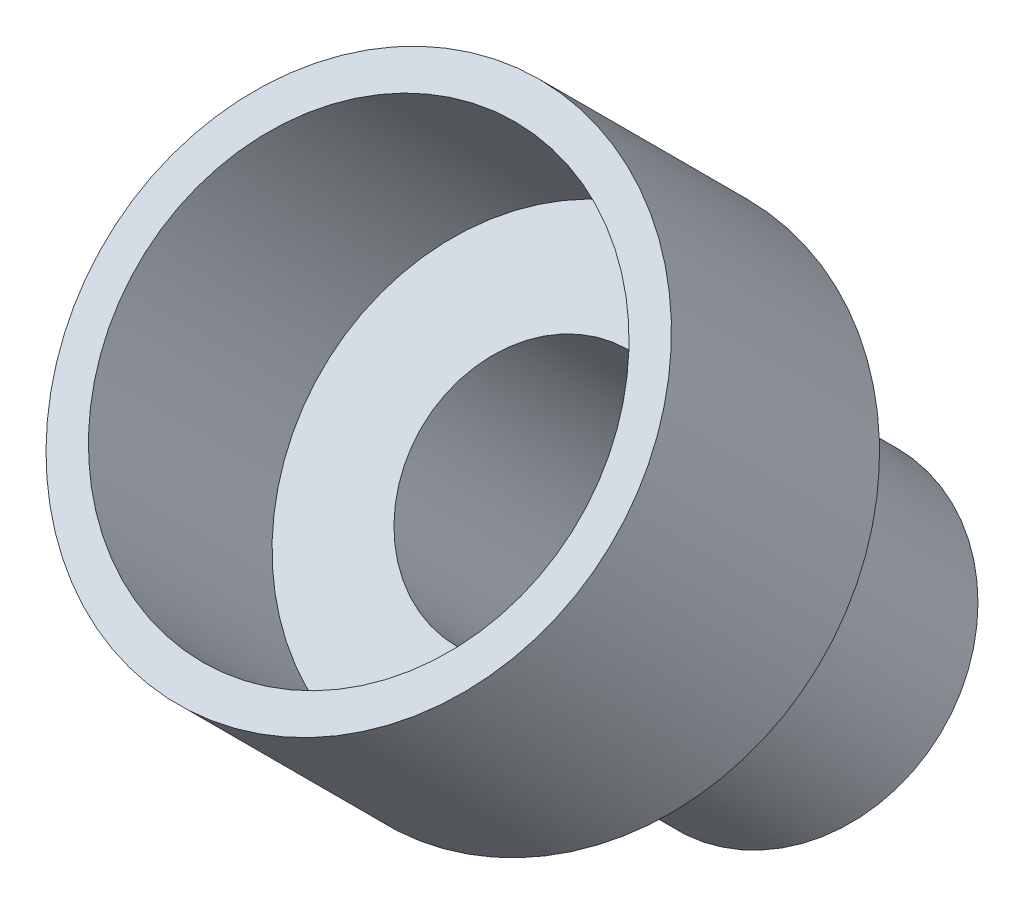
SolidWorks part; units mm, degrees
ref_plane "Front Plane" through (0, 0, 0) normal (0, 0, 1) x (1, 0, 0)
ref_plane "Top Plane" through (0, 0, 0) normal (0, 1, 0) x (1, 0, 0)
ref_plane "Right Plane" through (0, 0, 0) normal (1, 0, 0) x (0, 0, -1)
sketch "Sketch1" plane through (0, 0, 0) normal (1, 0, 0) x (0, 0, -1)
  line L0 (0, 0) -> (0, 92.1557) construction
  line L1 (0, 92.1557) -> (-111.3251, 203.4808) construction
  line L2 (0, 92.1557) -> (100.574, 192.7296) construction
  line L3 (-51.442, 125.5665) -> (-40.8354, 114.9599)
  line L4 (-40.8354, 114.9599) -> (-36.7696, 119.0257)
  line L5 (-36.7696, 119.0257) -> (-22.6274, 104.8836)
  line L6 (-22.6274, 104.8836) -> (-24.0416, 103.4694)
  line L7 (-51.442, 125.5665) -> (-52.8562, 124.1522)
  line L8 (-52.8562, 124.1522) -> (-40.8354, 112.1314)
  line L9 (-40.8354, 112.1314) -> (-36.7696, 116.1973)
  line L10 (-36.7696, 116.1973) -> (-24.0416, 103.4694)
  dimension "D1" = 90
  dimension "D2" = 135
  dimension "D3" = 25.5
  dimension "D4" = 15
  dimension "D5" = 14
  dimension "D6" = 20
  dimension "D7" = 25
  dimension "D8" = 2
  dimension "D9" = 2
  dimension "D10" = 2
revolve "Revolve1" add sketch "Sketch1" angle 360 about L1
sketch "Sketch2" plane through (0, 0, 0) normal (1, 0, 0) x (0, 0, -1)
  line L7 (-42.4264, 134.5821) -> (0, 92.1557) construction
  line L8 (0, 92.1557) -> (42.4264, 134.5821) construction
  line L9 (0, 92.1557) -> (0, 0) construction
  line L10 (-30, 104.5821) -> (-12.4264, 122.1557)
  line L11 (12.4264, 122.1557) -> (30.9634, 103.6187)
  line L12 (-30, 79.7293) -> (-12.4264, 62.1557)
  line L13 (12.4264, 62.1557) -> (30.9634, 80.6926)
  line L14 (-12.4264, 122.1557) -> (12.4264, 122.1557)
  line L16 (-30, 104.5821) -> (-30, 79.7293)
  line L17 (-12.4264, 62.1557) -> (12.4264, 62.1557)
  line L19 (-33.4108, 143.5977) -> (-51.442, 125.5665) construction
  line L21 (-11.3137, 116.1973) -> (-24.0416, 128.9252) construction
  line L22 (30.9634, 103.6187) -> (30.9634, 80.6926)
  circle A0 centre (0, 92.1557) radius 28.1134
  dimension "D1" = 30
  dimension "D2" = 30
  dimension "D3" = 30
  dimension "D5" = 30
extrude "Boss-Extrude1" [suppressed] add sketch "Sketch2" along normal blind 15 and the other way blind 15
pattern_circular "CirPattern1" count 2 every 90 of "Revolve1" reverse direction yes
sketch "Sketch4" [suppressed] plane through (0, 0, 0) normal (1, 0, 0) x (0, 0, -1)
  line L0 (0, 62.1557) -> (0, 3.1356) construction
  line L1 (-12.4264, 62.1557) -> (12.4264, 62.1557) construction
  line L2 (-14.5, 68.6222) -> (-14.5, 52.1557)
  line L3 (-14.5, 52.1557) -> (-24.5, 52.1557)
  line L4 (-24.5, 52.1557) -> (-24.5, 47.1557)
  line L6 (-16.5, 47.1557) -> (-16.5, 32.1557)
  line L7 (-16.5, 32.1557) -> (-20.5, 32.1557)
  line L8 (-20.5, 32.1557) -> (-20.5, 47.1557)
  line L10 (-12.5, 47.1557) -> (-12.5, 66.6222)
  line L11 (-14.5, 68.6222) -> (-12.5, 66.6222)
  line L12 (-24.5, 47.1557) -> (-20.5, 47.1557)
  line L13 (-16.5, 47.1557) -> (-12.5, 47.1557)
  dimension "D1" = 25
  dimension "D2" = 2
  dimension "D3" = 15
  dimension "D5" = 10
  dimension "D6" = 10
  dimension "D7" = 8
  dimension "D8" = 4
revolve "Revolve2" [suppressed] add sketch "Sketch4" angle 360 about L0
sketch "Sketch5" [suppressed] plane through (15, 0, 0) normal (1, 0, 0) x (0, 0, -1)
  circle A0 centre (0, 92.1557) radius 28.1134
extrude "Cut-Extrude1" [suppressed] cut sketch "Sketch5" against normal blind 41
sketch "Sketch6" [suppressed] plane through (0, 67.291, 67.291) normal (0, 0.7071, 0.7071) x (1, 0, 0)
  circle A0 centre (0, 65.1639) radius 7
extrude "Cut-Extrude2" [suppressed] cut sketch "Sketch6" against normal blind 41
sketch "Sketch7" [suppressed] plane through (0, 67.291, -67.291) normal (0, 0.7071, -0.7071) x (1, 0, 0)
  circle A0 centre (0, -65.1639) radius 7
extrude "Cut-Extrude3" [suppressed] cut sketch "Sketch7" against normal blind 41
sketch "Sketch8" [suppressed] plane through (0, 62.1557, 0) normal (0, -1, 0) x (1, 0, 0)
  circle A0 centre (0, 0) radius 12.5
extrude "Cut-Extrude4" [suppressed] cut sketch "Sketch8" against normal blind 41
fillet "Fillet1" [suppressed] radius 3
sketch "Sketch9" [suppressed] plane through (15, 0, 0) normal (1, 0, 0) x (0, 0, -1)
  line L2 (-30, 104.5821) -> (-12.4264, 122.1557)
  line L3 (12.4264, 122.1557) -> (30.9634, 103.6187)
  line L4 (-30, 79.7293) -> (-12.4264, 62.1557)
  line L5 (12.4264, 62.1557) -> (30.9634, 80.6926)
  line L6 (-12.4264, 122.1557) -> (12.4264, 122.1557)
  line L7 (-30, 104.5821) -> (-30, 79.7293)
  line L8 (-12.4264, 62.1557) -> (12.4264, 62.1557)
  line L9 (30.9634, 103.6187) -> (30.9634, 80.6926)
extrude "Boss-Extrude2" [suppressed] add sketch "Sketch9" against normal blind 2
sketch "Sketch10" [suppressed] plane through (-15, 0, 0) normal (-1, 0, 0) x (0, 0, 1)
  line L2 (-30, 104.5821) -> (-12.4264, 122.1557)
  line L3 (12.4264, 122.1557) -> (30.9634, 103.6187)
  line L4 (-30, 79.7293) -> (-12.4264, 62.1557)
  line L5 (12.4264, 62.1557) -> (30.9634, 80.6926)
  line L6 (-12.4264, 122.1557) -> (12.4264, 122.1557)
  line L7 (-30, 104.5821) -> (-30, 79.7293)
  line L8 (-12.4264, 62.1557) -> (12.4264, 62.1557)
  line L9 (30.9634, 103.6187) -> (30.9634, 80.6926)
extrude "Boss-Extrude3" [suppressed] add sketch "Sketch10" against normal blind 2
fillet "Fillet2" [suppressed] radius 3
ref_plane "Plane1" [suppressed] through (0, 2.1557, 0) normal (0, -1, 0) x (-1, 0, 0)
sketch "Sketch11" [suppressed] plane through (0, 2.1557, 0) normal (0, -1, 0) x (-1, 0, 0)
  line L1 (0, 29.7335) -> (-25.75, 14.8668)
  line L2 (-25.75, 14.8668) -> (-25.75, -14.8668)
  line L3 (-25.75, -14.8668) -> (0, -29.7335)
  line L4 (0, -29.7335) -> (25.75, -14.8668)
  line L5 (25.75, -14.8668) -> (25.75, 14.8668)
  line L6 (25.75, 14.8668) -> (0, 29.7335)
  circle A0 centre (0, 0) radius 19.75
  circle A1 centre (0, 0) radius 25.75 construction
  dimension "D1" = 6
  dimension "D2" = 39.5
extrude "Boss-Extrude4" [suppressed] add sketch "Sketch11" along normal blind 5 separate body contours L1 L2 L3 L4 L5 L6 | A0
sketch "Sketch12" [suppressed] plane through (0, 2.1557, 0) normal (0, 1, 0) x (1, 0, 0)
  circle A0 centre (0, 0) radius 32.5
  circle A1 centre (0, 0) radius 19.75
  dimension "D1" = 65
  dimension "D2" = 39.5
extrude "Boss-Extrude5" [suppressed] add sketch "Sketch12" along normal blind 3
ref_plane "Plane2" [suppressed] through (0, -32.8443, 0) normal (0, -1, 0) x (-1, 0, 0)
sketch "Sketch15" [suppressed] plane through (0, -32.8443, 0) normal (0, -1, 0) x (-1, 0, 0)
  circle A0 centre (0, 0) radius 19.75
curve "Helix/Spiral1" [suppressed] pitch 3 height 78.75 turns 26.25
sketch "Sketch16" [suppressed] plane through (0, 0, 0) normal (1, 0, 0) x (0, 0, -1)
  line L0 (0, 0) -> (0, -46.8329) construction
  line L1 (-28.325, -32.8443) -> (28.325, -32.8443) construction
  line L2 (-21.25, -32.0943) -> (-19.75, -32.0943)
  line L3 (-21.25, -32.0943) -> (-21.25, -33.5943)
  line L4 (-21.25, -33.5943) -> (-19.75, -33.5943)
  line L5 (-19.75, -32.0943) -> (-19.75, -33.5943)
  line L6 (-21.25, -32.0943) -> (-19.75, -33.5943) construction
  line L7 (-21.25, -33.5943) -> (-19.75, -32.0943) construction
  point P3 (-20.5, -32.8443)
  point P10 (-20.5, -33.5943)
  dimension "D1" = 20.5
  dimension "D2" = 1.5
  dimension "D3" = 1.5
sweep "Cut-Sweep1" [suppressed] cut profiles "Sketch16" path "Helix/Spiral1"
